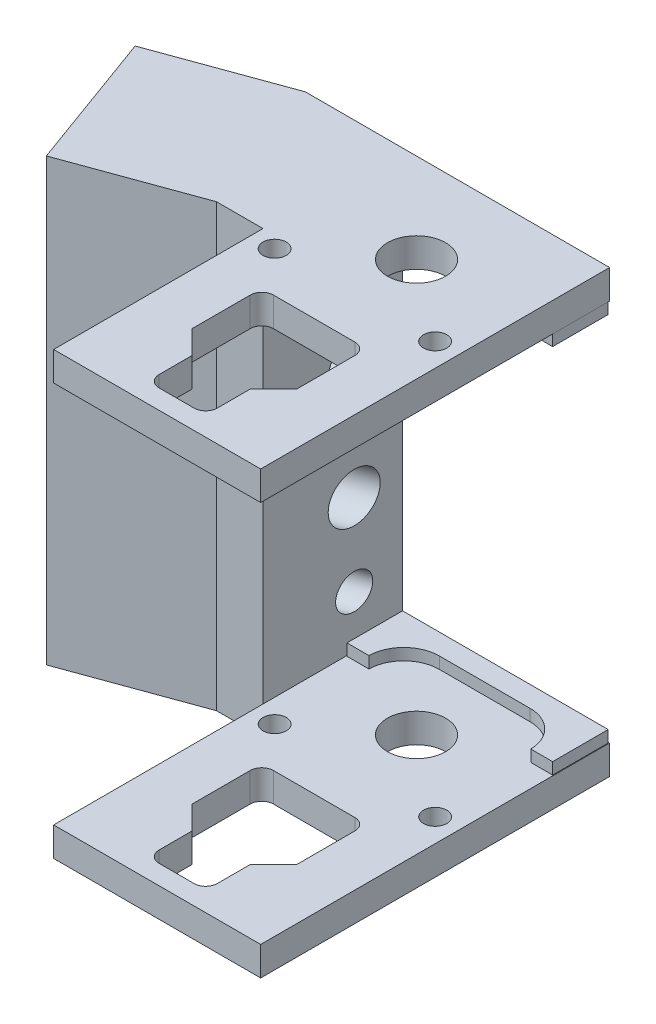
SolidWorks part; units mm, degrees
ref_plane "Płaszczyzna przednia" through (0, 0, 0) normal (0, 0, 1) x (1, 0, 0)
ref_plane "Płaszczyzna górna" through (0, 0, 0) normal (0, 1, 0) x (1, 0, 0)
ref_plane "Płaszczyzna prawa" through (0, 0, 0) normal (1, 0, 0) x (0, 0, -1)
sketch "Sketch1" plane through (0, 0, 0) normal (0, 1, 0) x (1, 0, 0)
  line L0 (-6.9, 0) -> (6.9, 0) construction
  line L2 (-8.9, 13) -> (8.9, 13)
  line L3 (-8.9, 13) -> (-8.9, -17)
  line L4 (-8.9, -17) -> (8.9, -17)
  line L5 (8.9, 13) -> (8.9, -17)
  circle A0 centre (-6.9, 0) radius 1
  circle A1 centre (6.9, 0) radius 1
  circle A2 centre (6.9, 0) radius 2 construction
  circle A3 centre (-6.9, 0) radius 2 construction
  circle A4 centre (0, 5.3) radius 2.5
  point P4 (0, 0)
  dimension "D2" = 2
  dimension "D4" = 5
  dimension "D5" = 5.3
  dimension "D1" = 13.8
  dimension "D6" = 13
  dimension "D7" = 17
  dimension "D3" = 1
extrude "Boss-Extrude1" add sketch "Sketch1" along normal blind 2.5
sketch "Sketch2" plane through (0, 2.5, 0) normal (0, 1, 0) x (1, 0, 0)
  line L0 (0, -3.5) -> (0, 0) construction
  line L1 (-4.5, -3.5) -> (4.5, -3.5)
  line L2 (-4.5, -3.5) -> (-4.5, -9.5)
  line L3 (-4.5, -9.5) -> (4.5, -9.5)
  line L4 (4.5, -3.5) -> (4.5, -9.5)
  line L5 (0, -15.3309) -> (0, 0) construction
  line L6 (-2.5, -9.5) -> (2.5, -9.5)
  line L7 (-2.5, -9.5) -> (-2.5, -15.3309)
  line L8 (-2.5, -15.3309) -> (2.5, -15.3309)
  line L9 (2.5, -9.5) -> (2.5, -15.3309)
  dimension "D1" = 9
  dimension "D2" = 6
  dimension "D3" = 3.5
  dimension "D4" = 5
extrude "Cut-Extrude1" cut sketch "Sketch2" against normal through all contours L4 L1 L2 L3 | L9 L3 L7 L8 region at (0, 2.5, 6.5) region at (0, 2.5, 12.4155)
chamfer "Chamfer1" distance 2 angle 45 2 edges at (2.5, 1.25, 9.5) (-2.5, 1.25, 9.5)
fillet "Fillet1" radius 1 4 edges at (2.5, 1.25, 15.3309) (-2.5, 1.25, 15.3309) (4.5, 1.25, 3.5) (-4.5, 1.25, 3.5)
sketch "Sketch3" plane through (0, 2.5, 0) normal (0, 1, 0) x (1, 0, 0)
  line L0 (-3.9, 11.1) -> (3.9, 11.1) construction
  line L1 (-3.9, 11.1) -> (3.9, 11.1) construction
  line L2 (-6.9, 8.1) -> (-8.9, 8.1) construction
  line L3 (-8.9, 13) -> (-8.9, -17) construction
  line L4 (-8.9, 8.1) -> (-8.9, 13) construction
  line L5 (-8.9, 13) -> (8.9, 13) construction
  line L6 (8.9, 13) -> (8.9, 8.1) construction
  line L7 (8.9, -17) -> (8.9, 13) construction
  line L8 (8.9, 8.1) -> (6.9, 8.1) construction
  line L9 (8.84, 8.16) -> (6.9594, 8.16)
  line L10 (-3.9, 11.16) -> (3.9, 11.16)
  line L11 (-6.9594, 8.16) -> (-8.84, 8.16)
  line L12 (-8.84, 8.16) -> (-8.84, 12.94)
  line L13 (-8.84, 12.94) -> (8.84, 12.94)
  line L14 (8.84, 12.94) -> (8.84, 8.16)
  arc A0 (6.9, 8.1) -> (3.9, 11.1) centre (3.8989, 8.0989) ccw construction
  arc A1 (-3.9, 11.1) -> (-6.9, 8.1) centre (-3.8989, 8.0989) ccw construction
  arc A2 (6.9, 8.1) -> (3.9, 11.1) centre (3.8989, 8.0989) ccw construction
  arc A3 (-3.9, 11.1) -> (-6.9, 8.1) centre (-3.8989, 8.0989) ccw construction
  arc A4 (6.9594, 8.16) -> (3.9, 11.16) centre (3.8989, 8.0989) ccw
  arc A5 (-3.9, 11.16) -> (-6.9594, 8.16) centre (-3.8989, 8.0989) ccw
  dimension "D1" = 0.06
extrude "Boss-Extrude2" add sketch "Sketch3" along normal blind 1
ref_plane "Plane1" through (0, 18.95, 0) normal (0, 1, 0) x (1, 0, 0)
sketch "Sketch4" plane through (-8.9, 0, 0) normal (-1, 0, 0) x (0, 0, 1)
  line L0 (9.79, 18.95) -> (-9.79, 18.95) construction
  line L1 (-13, 0) -> (-1, 0)
  line L2 (-13, 0) -> (-13, 18.95)
  line L3 (-13, 18.95) -> (-1, 18.95)
  line L4 (-1, 0) -> (-1, 18.95)
  dimension "D1" = 12
extrude "Boss-Extrude3" add sketch "Sketch4" along normal blind 4
mirror "Mirror2" about plane through (0, 18.95, 0) normal (0, 1, 0) of bodies 104
sketch "Sketch5" plane through (0, 37.9, 0) normal (0, 1, 0) x (1, 0, 0)
  line L0 (-12.9, 1) -> (-17.2676, 13)
  line L1 (-17.2676, 13) -> (-12.9, 13)
  line L2 (-12.9, 13) -> (-12.9, 1)
  dimension "D1" = 20
extrude "Boss-Extrude4" add sketch "Sketch5" against normal up to surface (37.9 mm away) up to face at (0, 0, -2.8)
sketch "Sketch6" plane through (-11.0696, 0, 4.029) normal (-0.9397, 0, 0.342) x (0.342, 0, 0.9397)
  line L4 (-18.1219, 0) -> (-5.3518, 0)
  line L5 (-5.3518, 0) -> (-5.3518, 37.9)
  line L6 (-5.3518, 37.9) -> (-18.1219, 37.9)
  line L7 (-18.1219, 37.9) -> (-18.1219, 0)
  line L8 (-18.1219, 0) -> (-5.3518, 0)
  line L9 (-5.3518, 0) -> (-5.3518, 37.9)
  line L10 (-5.3518, 37.9) -> (-18.1219, 37.9)
  line L11 (-18.1219, 37.9) -> (-18.1219, 0)
  dimension "D1" = 0
extrude "Boss-Extrude5" add sketch "Sketch6" along normal blind 11.41
hole_wizard "Ø3.0 mm Dowel Holes1" positions "Sketch7" profile "Sketch9" hole size "Ø3.0" standard "DIN" end condition through all
sketch "Sketch7" plane through (-23.7268, 0, 2.6144) normal (0.9397, 0, -0.342) x (-0.342, 0, -0.9397)
  line L1 (9.6016, 18.95) -> (-0.3066, 18.95) construction
  line L2 (9.6016, 35.4) -> (9.6016, 2.5) construction
  line L3 (-0.3066, 0) -> (-0.3066, 37.9) construction
  line L4 (5.6934, 30.95) -> (5.6934, 18.95)
  line L6 (-0.3066, 0) -> (-0.3066, 37.9) construction
  point P11 (5.6934, 30.95)
  point P19 (5.6934, 6.95)
  point P22 (0, 0)
  dimension "D1" = 12
  dimension "D2" = 6
sketch "Sketch9" plane through (-25.674, 6.95, -2.7357) normal (0, 1, 0) x (0.342, 0, 0.9397)
  line L0 (0, 0) -> (0, 35.9995)
  line L1 (0, 35.9995) -> (1.5, 35.9995)
  line L2 (1.5, 35.9995) -> (1.5, 0)
  line L5 (1.5, 0) -> (0, 0)
  line L11 (0, -6.35) -> (0, 107.95) construction
  dimension "Thru Hole Dia." = 3
  dimension "Thru Hole Depth" = 35.9995
hole_wizard "Ø4.2 (4.2) Diameter Hole1" positions "Sketch10" profile "Sketch11" hole size "Ø4.2" standard "DIN" end condition through all
sketch "Sketch10" plane through (-21.7915, 0, 7.9315) normal (-0.9397, 0, 0.342) x (0.342, 0, 0.9397)
  line L0 (-11.3518, 30.95) -> (-11.3518, 23.95)
  line L1 (-11.3518, 23.95) -> (-11.3518, 30.95)
  line L3 (-11.3518, 13.95) -> (-11.3518, 6.95)
  line L5 (-11.3518, 13.95) -> (-11.3518, 6.95)
  circle A0 centre (-11.3518, 23.95) radius 4
  point P7 (-11.3518, 23.95)
  point P9 (-11.3518, 13.95)
  dimension "D2" = 8
  dimension "D1" = 10
sketch "Sketch11" plane through (-25.674, 13.95, -2.7357) normal (0, 1, 0) x (0.342, 0, 0.9397)
  line L0 (0, 0) -> (0, 35.9995)
  line L1 (0, 35.9995) -> (2.1, 35.9995)
  line L2 (2.1, 35.9995) -> (2.1, 0)
  line L5 (2.1, 0) -> (0, 0)
  line L11 (0, -6.35) -> (0, 107.95) construction
  dimension "Thru Hole Dia." = 4.2
  dimension "Thru Hole Depth" = 35.9995
